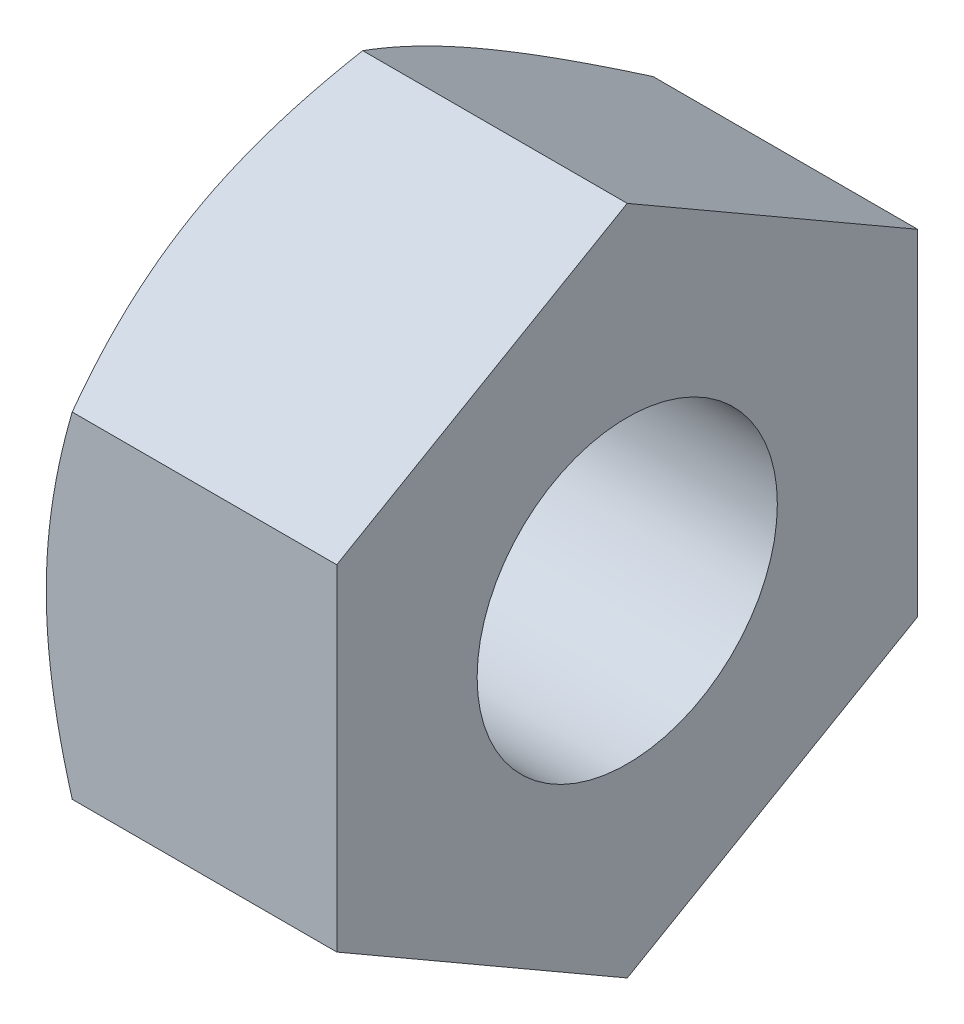
SolidWorks part; units mm, degrees
note: '?' marks a value the reader was unsure of.
ref_plane "Front Plane" through (0, 0, 0) normal (0, 0, 1) x (1, 0, 0)
ref_plane "Top Plane" through (0, 0, 0) normal (0, 1, 0) x (1, 0, 0)
ref_plane "Right Plane" through (0, 0, 0) normal (1, 0, 0) x (0, 0, -1)
ref_axis "Axis_X" through (-4.2, 0, 0) along (1, 0, 0)?
ref_axis "Axis_Y" through (0, 5.0807, 0) along (0, -1, 0)?
ref_axis "Axis_Z" through (0, 0, -4.4) along (0, 0, 1)?
ref_plane "Dim.M" through (5, 0, 0) normal (1, 0, 0) x (0, 0, -1)
sketch "Sketch1" plane through (0, 0, 0) normal (1, 0, 0) x (0, 0, -1)
  line L1 (0, 4.6188) -> (-4, 2.3094)
  line L2 (-4, 2.3094) -> (-4, -2.3094)
  line L3 (-4, -2.3094) -> (0, -4.6188)
  line L4 (0, -4.6188) -> (4, -2.3094)
  line L5 (4, -2.3094) -> (4, 2.3094)
  line L6 (4, 2.3094) -> (0, 4.6188)
  circle A0 centre (0, 0) radius 4 construction
  dimension "B" = 8
extrude "Boss-Extrude1" add sketch "Sketch1" against normal blind 4
sketch "Sketch2" plane through (0, 0, 0) normal (0, 0, 1) x (1, 0, 0)
  line L0 (-2.2385, 0) -> (0.6157, 0) construction
  line L1 (-4, 4) -> (-3.6427, 4.6188)
  line L2 (-4, 4.6188) -> (-4, 2.3094) construction
  line L3 (-4, 4.6188) -> (0, 4.6188) construction
  line L4 (-3.6427, 4.6188) -> (-4, 4.6188)
  line L5 (-4, 4.6188) -> (-4, 4)
  dimension "B" = 8
  dimension "FIX_1" = 30
revolve "Cut-Revolve1" cut sketch "Sketch2" about L0
hole_wizard "Tap1" positions "Sketch4" profile "Sketch3" hole size "M1x0.25" standard "JIS" end condition up to next
sketch "Sketch4" plane through (-4, 0, 0) normal (-1, 0, 0) x (0, 0, 1)
  point P0 (0, 0)
sketch "Sketch3" plane through (-4, 0, 0) normal (0, 1, 0) x (0, 0, 1)
  line L0 (0, 0) -> (0, 4)
  line L1 (0, 4) -> (2.067, 4)
  line L2 (2.067, 4) -> (2.067, 0)
  line L5 (2.067, 0) -> (0, 0)
  line L11 (0, 0) -> (0, 4) construction
  dimension "Thru Hole Depth" = 4
  dimension "HSD_1" = 4.134
other "DeleteFace1" [suppressed]
sketch "Sketch5" plane through (0, 0, 0) normal (0, 0, 1) x (1, 0, 0)
  line L0 (-1.2, 4) -> (-0.8427, 4.6188)
  line L3 (-0.8427, 4.6188) -> (-1.2, 4.6188)
  line L4 (-1.2, 4.6188) -> (-1.2, 4) construction
  line L5 (0, 4) -> (-0.3573, 4.6188)
  line L6 (0, 4.6188) -> (0, 2.3094) construction
  line L7 (-0.3573, 4.6188) -> (0, 4.6188)
  line L8 (0, 4.6188) -> (0, 4)
  line L9 (-1.687, 0) -> (0.4573, 0) construction
  line L10 (-1.2, 4.6188) -> (-6.2, 4.6188)
  line L11 (-6.2, 4.6188) -> (-6.2, 0)
  line L12 (-6.2, 0) -> (-1.2, 0)
  line L13 (-1.2, 0) -> (-1.2, 4)
  dimension "D1" = 5
  dimension "B" = 8
  dimension "T1" = 1.2
revolve "Cut-Revolve2" [suppressed] cut sketch "Sketch5" about L9
hole_wizard "Tap2" [suppressed] positions "Sketch6" profile "Sketch7" hole size "M1.6x0.35" standard "JIS"
sketch "Sketch6" plane through (0, 0, 0) normal (1, 0, 0) x (0, 0, -1)
  point P0 (0, 0)
sketch "Sketch7" plane through (0, 0, 0) normal (0, 1, 0) x (0, 0, -1)
  line L0 (0, 0) -> (0, 1.2)
  line L1 (0, 1.2) -> (0.7835, 1.2)
  line L2 (0.7835, 1.2) -> (0.7835, 0)
  line L5 (0.7835, 0) -> (0, 0)
  line L11 (0, 0) -> (0, 1.2) construction
  dimension "Thru Hole Depth" = 1.2
  dimension "HSD_1" = 4.134
equation "\"Factor\"= 1.082532"
equation "\"Pitch_M\"= IIF ( \"M\" = 24 , 3 , IIF ( \"M\" = 20 , 2.5 , IIF ( \"M\" = 16 , 2 , IIF ( \"M\" = 12 , 1.75 , IIF ( \"M\" = 10 , 1.5 , IIF ( \"M\" = 8 , 1.25 , IIF ( \"M\" = 6 , 1 , IIF ( \"M\" = 5 , 0.8 , IIF ( \"M\" = 4 , 0.7 , IIF ( \"M\" = 3 , 0.5 , IIF ( \"M\" = 2.6 , 0.45 , IIF ( \"M\" = 2.5 , 0.45 , IIF ( \"M\" = 2 , 0.4 , 0.4 ) ) ) ) ) ) ) ) ) ) ) ) )"
equation "\"HSD_1\"= round ( \"M\" - \"Factor\" * \"Pitch_M\" , 3 )"
